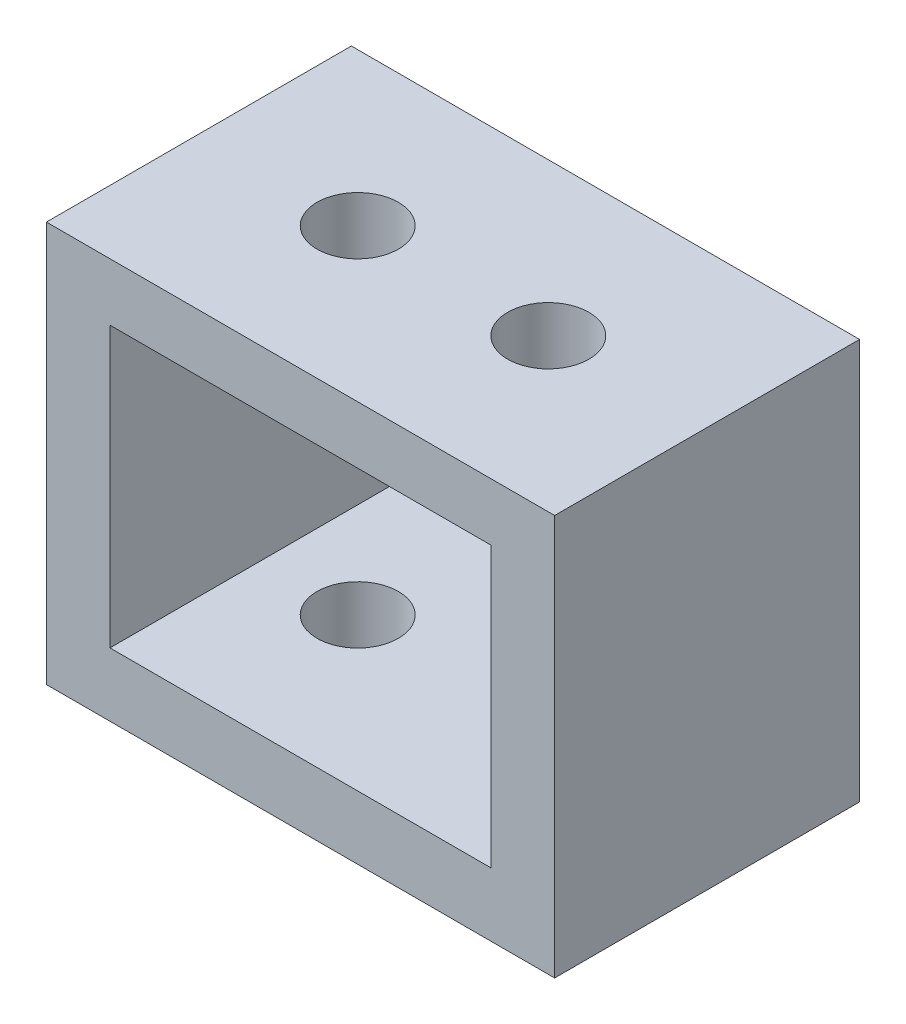
SolidWorks part; units mm, degrees
note: The reader was unsure of these and kept them because the rebuilt part matched: shared geometry of "Sketch1<5>".
material "ABS"
ref_plane "Front Plane" through (0, 0, 0) normal (0, 0, 1) x (1, 0, 0)
ref_plane "Top Plane" through (0, 0, 0) normal (0, 1, 0) x (1, 0, 0)
ref_plane "Right Plane" through (0, 0, 0) normal (1, 0, 0) x (0, 0, -1)
sketch "Sketch1" plane through (0, 0, 0) normal (0, 1, 0) x (1, 0, 0)
  line L0 (15, -12) -> (-15, 12) construction
  line L1 (15, 12) -> (-15, -12) construction
  line L7 (-15, 12) -> (15, 12)
  line L8 (-15, 12) -> (-15, -12)
  line L9 (-15, -12) -> (15, -12)
  line L10 (15, 12) -> (15, -12)
  point P6 (0, 0)
  dimension "D3" = 24
  dimension "D4" = 30
extrude "Base-superior" add sketch "Sketch1" along normal blind 5
sketch "Esboço2" plane through (0, 0, 0) normal (1, 0, 0) x (0, 0, -1)
  line L0 (12, 5) -> (-12, 5) construction
  line L1 (-12, 30) -> (12, 30)
  line L2 (-12, 30) -> (-12, -27)
  line L3 (-12, -27) -> (12, -27)
  line L4 (12, 30) -> (12, -27)
  line L5 (12, 5) -> (12, 0) construction
  line L6 (12, 0) -> (-12, 0) construction
  line L7 (-12, 5) -> (-12, 0) construction
  dimension "D1" = 27
  dimension "D2" = 25
extrude "Placa-lateral" add sketch "Esboço2" along normal blind 5 from vertex at 15 starting at point (15, 5, 12)
extrude "Base-inferior" add sketch "Sketch1<5>" along normal blind 5 from vertex
sketch "Sketch1<5>" plane through (0, 0, 0) normal (0, 1, 0) x (1, 0, 0) same geometry as "Sketch1"
sketch "Sketch7" plane through (0, 0, 0) normal (0, -1, 0) x (1, 0, 0)
  circle A0 centre (-7.5, 0) radius 3.2
  circle A1 centre (7.5, 0) radius 3.2
  dimension "D1" = 6.4
  dimension "D2" = 6.4
  dimension "D4" = 15
  dimension "D5" = 7.5
extrude "Furo-Parafuso" cut sketch "Sketch7" against normal through all both and the other way through all
sketch "Furo-Cabeça-Parafuso" plane through (0, 5, 0) normal (0, 1, 0) x (1, 0, 0)
  circle A0 centre (7.5, 0) radius 5.75
  circle A1 centre (-7.5, 0) radius 5.75
  dimension "D1" = 11.5
  dimension "D2" = 11.5
sketch "Esboço3" plane through (20, 0, 0) normal (1, 0, 0) x (0, 0, -1)
  line L0 (12, -27) -> (12, 30) construction
  line L1 (12, 30) -> (-12, 30) construction
  line L2 (-8, 30) -> (8, 30)
  line L3 (171.9642, 12.9971) -> (0.7947, 38.0125) construction
  line L4 (171.9642, 12.9971) -> (3.1989, -24.9907) construction
  line L5 (171.9642, 12.9971) -> (1.4421, -16.1061) construction
  line L6 (171.9642, 12.9971) -> (0.1526, -7.1418) construction
  line L7 (171.9642, 12.9971) -> (-0.6659, 1.8777) construction
  line L8 (171.9642, 12.9971) -> (-1.0112, 10.9277) construction
  line L9 (171.9642, 12.9971) -> (-0.8825, 19.9834) construction
  line L10 (171.9642, 12.9971) -> (-0.28, 29.0199) construction
  arc A0 (-8, 30) -> (-4.3806, -26.7362) centre (171.9642, 12.9971) ccw
  arc A1 (12, -26.8126) -> (8, 30) centre (171.9642, 12.9971) cw
  arc A2 (-8, 30) -> (-6.8958, 39.1753) centre (171.9642, 12.9971) cw
  arc A3 (8, 30) -> (8.8585, 36.8695) centre (171.9642, 12.9971) cw
  arc A4 (12, -26.8126) -> (11.1522, -23.2364) centre (171.9642, 12.9971) ccw
  circle A5 centre (0.7947, 38.0125) radius 3
  arc A6 (-6.8958, 39.1753) -> (8.8585, 36.8695) centre (0.9813, 38.0224) cw
  arc A7 (11.1522, -23.2364) -> (-4.3806, -26.7362) centre (3.3858, -24.9863) cw
  arc A8 (5.1357, -32.7527) -> (2.1343, 45.8996) centre (171.9642, 12.9971) cw construction
  circle A9 centre (3.1989, -24.9907) radius 3
  circle A10 centre (1.4421, -16.1061) radius 3
  circle A11 centre (0.1526, -7.1418) radius 3
  circle A12 centre (-0.6659, 1.8777) radius 3
  circle A13 centre (-1.0112, 10.9277) radius 3
  circle A14 centre (-0.8825, 19.9834) radius 3
  circle A15 centre (-0.28, 29.0199) radius 3
  dimension "D4" = 6
  dimension "D6" = 6
  dimension "D14" = 6
  dimension "D15" = 6
  dimension "D16" = 6
  dimension "D17" = 6
  dimension "D18" = 6
  dimension "D19" = 6
  dimension "D3" = 4
  dimension "D1" = 4
  dimension "D5" = 8
  dimension "D7" = 8
  dimension "D8" = 3
  dimension "D9" = 6
  dimension "D2" = 9
  dimension "D10" = 12
  dimension "D11" = 15
  dimension "D12" = 18
  dimension "D13" = 21
fillet "Filete-interno" radius 7 1 edges at (15, 5, 0)
extrude "Rebaixo-cabeça-parafuso" cut sketch "Furo-Cabeça-Parafuso" along normal through all
sketch "Furo-vareta" plane through (0, 0, 0) normal (1, 0, 0) x (0, 0, -1)
  circle A0 centre (-0.6067, 25) radius 3
  arc A1 (2.1343, 45.8996) -> (5.1357, -32.7527) centre (171.9642, 12.9971) ccw construction
  dimension "D1" = 6
  dimension "D2" = 20
extrude "Furo-Vareta8mm" cut sketch "Furo-vareta" against normal through all both and the other way through all
fillet "Filete1" radius 10 2 edges at (17.5, 30, -12) (17.5, 30, 12)
mirror "Espelhar-Peça-Central" about plane through (0, 0, 0) normal (1, 0, 0) of bodies 120
sketch "Esboço4" plane through (0, 0, 0) normal (0, 0, 1) x (1, 0, 0)
  line L0 (20, 20) -> (20, -27) construction
  line L1 (-20, 30) -> (20, 30)
  line L2 (-20, 30) -> (-20, 4.5268)
  line L3 (-20, 4.5268) -> (20, 4.5268)
  line L4 (20, 30) -> (20, 4.5268)
extrude "Corte-extrusão1" cut sketch "Esboço4" against normal through all both and the other way through all
equation "\"D2@Furo-Cabeça-Parafuso\" = \"D1@Furo-Cabeça-Parafuso\""
equation "\"D1@Sketch7\"=\"D2@Sketch7\""
equation "\"D14@Esboço3\"=\"D6@Esboço3\""
equation "\"D15@Esboço3\"=\"D6@Esboço3\""
equation "\"D16@Esboço3\"=\"D6@Esboço3\""
equation "\"D17@Esboço3\"=\"D6@Esboço3\""
equation "\"D18@Esboço3\"=\"D6@Esboço3\""
equation "\"D19@Esboço3\"=\"D6@Esboço3\""
equation "\"D4@Esboço3\"=\"D6@Esboço3\""
